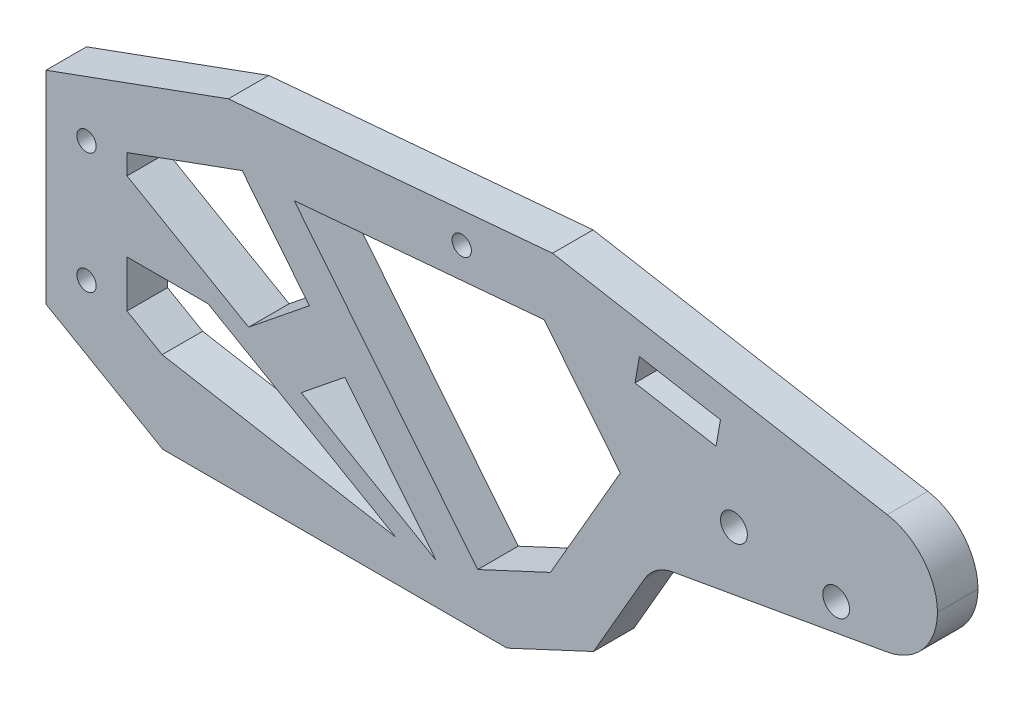
SolidWorks part; units mm, degrees
ref_plane "Plan de face" through (0, 0, 0) normal (0, 0, 1) x (1, 0, 0)
ref_plane "Plan de dessus" through (0, 0, 0) normal (0, 1, 0) x (1, 0, 0)
ref_plane "Plan de droite" through (0, 0, 0) normal (1, 0, 0) x (0, 0, -1)
sketch "Esquisse1" plane through (0, 0, 0) normal (0, 0, 1) x (1, 0, 0)
  line L1 (0, 0) -> (220, 0)
  line L2 (0, 0) -> (0, 90)
  line L3 (0, 90) -> (220, 90)
  line L4 (220, 0) -> (220, 90)
  dimension "D1" = 90
  dimension "D2" = 220
extrude "Boss.-Extru.1" add sketch "Esquisse1" along normal blind 10 contours L3 L4 L1 L2
sketch "Esquisse2" plane through (0, 0, 10) normal (0, 0, 1) x (1, 0, 0)
  line L0 (220, 73.2489) -> (125, 90)
  line L1 (220, 0) -> (220, 90) construction
  line L2 (0, 90) -> (220, 90) construction
  line L3 (125, 90) -> (45, 83.0009)
  line L4 (45, 83.0009) -> (0, 66.6222)
  line L5 (0, 0) -> (0, 90) construction
  line L6 (0, 66.6222) -> (0, 16.6222)
  line L7 (0, 16.6222) -> (28.7906, 0)
  line L8 (0, 0) -> (220, 0) construction
  line L9 (28.7906, 0) -> (113.7906, 0)
  line L10 (113.7906, 0) -> (135.1213, 9.9467)
  line L11 (135.1213, 9.9467) -> (150.1213, 35.9274)
  line L12 (150.1213, 35.9274) -> (220, 48.2489)
  line L13 (220, 48.2489) -> (220, 73.2489)
  dimension "D1" = 10
  dimension "D2" = 10
  dimension "D3" = 25
  dimension "D4" = 30
  dimension "D5" = 15
  dimension "D6" = 5
  dimension "D7" = 25
  dimension "D8" = 50
  dimension "D9" = 45
  dimension "D10" = 95
  dimension "D11" = 15
  dimension "D12" = 85
extrude "Enlèv. mat.-Extru.1" cut sketch "Esquisse2" against normal through all flip side to cut
sketch "Esquisse3" plane through (0, 0, 10) normal (0, 0, 1) x (1, 0, 0)
  line L0 (124.4956, 21.5425) -> (141.7327, 51.398)
  line L1 (141.7327, 51.398) -> (122.9121, 74.76)
  line L2 (122.9121, 74.76) -> (61.2631, 69.3664)
  line L3 (61.2631, 69.3664) -> (106.537, 13.1682)
  line L4 (96.248, 10) -> (73.7768, 37.8934)
  line L5 (73.7768, 37.8934) -> (62.9886, 29.2023)
  line L6 (62.9886, 29.2023) -> (96.248, 10)
  line L8 (20, 25.1543) -> (20, 36.7013)
  line L9 (20, 36.7013) -> (40, 36.7013)
  line L10 (40, 36.7013) -> (86.248, 10)
  line L11 (20, 54.0218) -> (49.9982, 36.7023)
  line L12 (49.9982, 36.7023) -> (65, 48.7879)
  line L13 (65, 48.7879) -> (48.4217, 69.3664)
  line L14 (48.4217, 69.3664) -> (20, 59.0218)
  line L15 (20, 59.0218) -> (20, 54.0218)
  line L16 (125, 90) -> (45, 83.0009) construction
  line L17 (135.1213, 9.9467) -> (150.1213, 35.9274) construction
  line L18 (0, 16.6222) -> (28.7906, 0) construction
  line L19 (113.7906, 0) -> (135.1213, 9.9467) construction
  line L20 (28.6603, 20.1543) -> (86.248, 10)
  line L21 (45, 83.0009) -> (0, 66.6222) construction
  line L22 (0, 16.6222) -> (0, 66.6222) construction
  line L23 (106.537, 13.1682) -> (124.4956, 21.5425)
  line L24 (28.7906, 0) -> (113.7906, 0) construction
  line L25 (20, 25.1543) -> (28.6603, 20.1543)
  dimension "D1" = 10
  dimension "D2" = 30
  dimension "D3" = 5
  dimension "D4" = 20
  dimension "D5" = 45
  dimension "D6" = 10
  dimension "D7" = 20
  dimension "D9" = 15
  dimension "D10" = 5
  dimension "D11" = 15
  dimension "D12" = 15
  dimension "D13" = 20
  dimension "D14" = 15
  dimension "D15" = 10
  dimension "D16" = 20
extrude "Enlèv. mat.-Extru.2" cut sketch "Esquisse3" against normal through all
fillet "Congé1" radius 15 2 edges at (220, 73.2489, 5) (220, 48.2489, 5)
sketch "Esquisse4" plane through (0, 0, 10) normal (0, 0, 1) x (1, 0, 0)
  line L0 (194.9998, 50.5372) -> (194.9998, 77.6572) construction
  line L1 (207.6047, 75.4346) -> (125, 90) construction
  circle A0 centre (194.9998, 50.5372) radius 3.305
  circle A1 centre (169.7666, 53.837) radius 3.305
  point P8 (0, 0)
  dimension "D1" = 6.61
  dimension "D2" = 25
  dimension "D4" = 25.2331
  dimension "D3" = 27.12
  dimension "D5" = 3.2998
extrude "Enlèv. mat.-Extru.3" cut sketch "Esquisse4" against normal through all
hole_wizard "Perçage pour écrous auto-bloquants 300® #6 (SP)1" positions "Esquisse5" profile "Esquisse6" hole size "#6-32" standard "PEM® Inch" end condition through all
sketch "Esquisse5" plane through (0, 0, 10) normal (0, 0, 1) x (1, 0, 0)
  line L21 (102.9121, 73.0103) -> (102.5846, 80.5103) construction
  line L22 (102.5846, 80.5103) -> (102.2572, 88.0103) construction
  line L24 (122.9121, 74.76) -> (61.2631, 69.3664) construction
  line L25 (125, 90) -> (45, 83.0009) construction
  point P41 (102.5846, 80.5103)
  dimension "D1" = 7.5
  dimension "D2" = 20
sketch "Esquisse6" plane through (102.5846, 80.5103, 10) normal (1, 0, 0) x (0, -1, 0)
  line L0 (0, 0) -> (0, 10)
  line L1 (0, 10) -> (2.3812, 10)
  line L2 (2.3812, 10) -> (2.3812, 0)
  line L5 (2.3812, 0) -> (0, 0)
  line L11 (0, -6.35) -> (0, 107.95) construction
  dimension "Diamètre du perçage jusqu'au prochain" = 4.7625
  dimension "Profondeur du perçage jusqu'au prochain" = 10
hole_wizard "Perçage pour écrous auto-bloquants 300® #6 (SP)2" positions "Esquisse8" profile "Esquisse9" hole size "#6-32" standard "PEM® Inch" end condition through all
sketch "Esquisse8" plane through (0, 0, 10) normal (0, 0, 1) x (1, 0, 0)
  line L0 (10, 56.5218) -> (0, 56.5218) construction
  line L1 (0, 16.6222) -> (0, 66.6222) construction
  line L3 (10, 56.5218) -> (20, 56.5218) construction
  line L4 (20, 59.0218) -> (20, 54.0218) construction
  line L6 (10, 56.5218) -> (10, 26.7227) construction
  point P0 (10, 56.5218)
  point P2 (10, 26.7227)
  point P23 (0, 41.6222)
  point P24 (10, 41.6222)
  point P26 (20, 56.5218)
sketch "Esquisse9" plane through (10, 56.5218, 10) normal (1, 0, 0) x (0, -1, 0)
  line L0 (0, 0) -> (0, 10)
  line L1 (0, 10) -> (2.3812, 10)
  line L2 (2.3812, 10) -> (2.3812, 0)
  line L5 (2.3812, 0) -> (0, 0)
  line L11 (0, -6.35) -> (0, 107.95) construction
  dimension "Diamètre du perçage jusqu'au prochain" = 4.7625
  dimension "Profondeur du perçage jusqu'au prochain" = 10
sketch "Esquisse10" plane through (0, 0, 10) normal (0, 0, 1) x (1, 0, 0)
  line L0 (146.451, 78.6628) -> (145.357, 72.4586)
  line L1 (146.451, 78.6628) -> (166.4426, 75.1378)
  line L2 (145.357, 72.4586) -> (165.3486, 68.9335)
  line L3 (166.4426, 75.1378) -> (165.3486, 68.9335)
  line L4 (155.3528, 70.696) -> (194.9998, 50.5372) construction
  line L6 (207.6047, 75.4346) -> (125, 90) construction
  dimension "D1" = 20.3
  dimension "D2" = 6.3
  dimension "D3" = 44.4777
  dimension "D4" = 7.44
extrude "Enlèv. mat.-Extru.4" cut sketch "Esquisse10" against normal blind 10 contours L1 L3 L2 L0
fillet "Congé2" radius 10 1 edges at (150.1213, 35.9274, 5)
